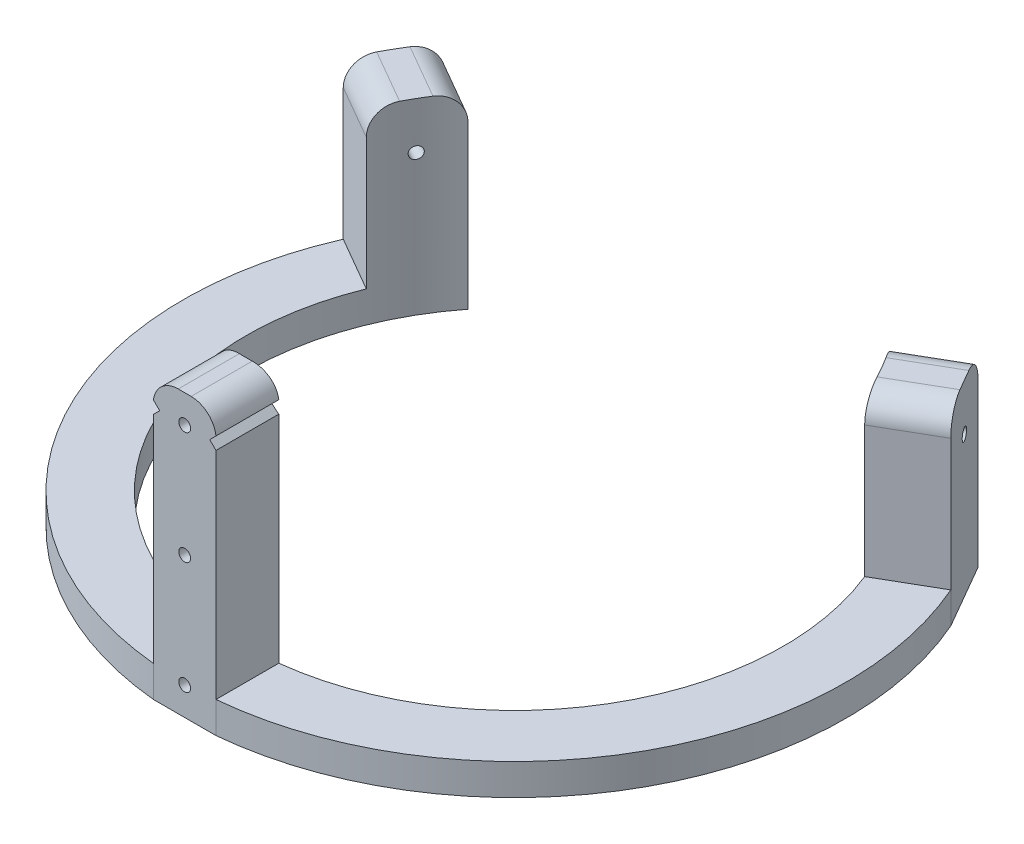
SolidWorks part; units mm, degrees
ref_plane "Front Plane" through (0, 0, 0) normal (0, 0, 1) x (1, 0, 0)
ref_plane "Top Plane" through (0, 0, 0) normal (0, 1, 0) x (1, 0, 0)
ref_plane "Right Plane" through (0, 0, 0) normal (1, 0, 0) x (0, 0, -1)
sketch "Sketch1" plane through (0, 0, 0) normal (0, 1, 0) x (1, 0, 0)
  circle A0 centre (0, 0) radius 54.61
  circle A2 centre (0, 0) radius 67.31
  dimension "D1" = 109.22
  dimension "D2" = 12.7
extrude "Boss-Extrude1" add sketch "Sketch1" along normal blind 57.15
ref_plane "Plane1" through (0, 0, 67.31) normal (0, 0, 1) x (1, 0, 0)
sketch "Sketch2" plane through (0, 0, 67.31) normal (0, 0, 1) x (1, 0, 0)
  line L0 (0, 57.15) -> (0, 0) construction
  line L1 (67.31, 57.15) -> (-67.31, 57.15) construction
  line L2 (0, 51.435) -> (5.08, 51.435) construction
  line L3 (0, 51.435) -> (-5.08, 51.435) construction
  line L4 (-6.35, 57.15) -> (-6.35, 52.705)
  line L5 (54.61, 57.15) -> (-54.61, 57.15) construction
  line L6 (-6.35, 52.705) -> (-5.08, 51.435)
  line L7 (-5.08, 51.435) -> (-6.35, 50.165)
  line L8 (-6.35, 50.165) -> (-6.35, 0)
  line L9 (-67.31, 0) -> (67.31, 0) construction
  line L10 (6.35, 0) -> (6.35, 50.165)
  line L11 (6.35, 50.165) -> (5.08, 51.435)
  line L12 (5.08, 51.435) -> (6.35, 52.705)
  line L13 (6.35, 52.705) -> (6.35, 57.15)
  line L15 (-6.35, 25.0825) -> (-19.05, 25.0825)
  line L16 (-6.35, 25.0825) -> (-6.35, 57.15)
  line L17 (-6.35, 57.15) -> (-19.05, 57.15)
  line L18 (-19.05, 25.0825) -> (-19.05, 57.15)
  line L19 (6.35, 25.0825) -> (19.05, 25.0825)
  line L20 (6.35, 25.0825) -> (6.35, 57.15)
  line L21 (6.35, 57.15) -> (19.05, 57.15)
  line L22 (19.05, 25.0825) -> (19.05, 57.15)
  circle A0 centre (0, 28.575) radius 1.2065
  circle A1 centre (0, 51.435) radius 1.2065
  circle A2 centre (0, 5.715) radius 1.2065
  dimension "D1" = 22.86
  dimension "D3" = 2.413
  dimension "D4" = 2.413
  dimension "D5" = 2.413
  dimension "D2" = 22.86
  dimension "D6" = 5.08
  dimension "D7" = 5.08
  dimension "D8" = 6.35
  dimension "D9" = 6.35
  dimension "D10" = 1.27
  dimension "D11" = 1.27
  dimension "D12" = 12.7
  dimension "D13" = 12.7
extrude "Cut-Extrude1" cut sketch "Sketch2" against normal through all both and the other way through all contours L16 L7 L6 | L18 L15 L8 L16 L4 L17 | L11 L20 L12 | L19 L22 L21 L13 L20 L10 | A1 | A0 | A2 region at (-12.7, 41.1162, 67.31) region at (-5.9267, 51.435, 67.31) region at (12.7, 41.1162, 67.31) region at (5.9267, 51.435, 67.31) region at (0, 28.575, 67.31) region at (0, 51.435, 67.31) region at (0, 5.715, 67.31)
ref_plane "Plane2" through (-58.2922, 0, -33.655) normal (-0.866, 0, -0.5) x (0, -1, 0)
sketch "Sketch3" plane through (-58.2922, 0, -33.655) normal (-0.866, 0, -0.5) x (0, -1, 0)
  line L0 (0, 0) -> (-57.15, 0) construction
  line L1 (0, -67.31) -> (0, 67.31) construction
  line L2 (-57.15, 67.31) -> (-57.15, -46.3839) construction
  line L3 (0, 0) -> (0, 67.31) construction
  line L4 (0, -67.31) -> (0, 67.31)
  circle A0 centre (-28.575, 0) radius 1.2065
  dimension "D1" = 2.413
extrude "Cut-Extrude2" cut sketch "Sketch3" against normal through all contours A0 region at (-58.2922, 28.575, -33.655)
mirror "Mirror1" about plane through (0, 0, 0) normal (1, 0, 0) of "Cut-Extrude2"
sketch "Sketch4" plane through (0, 57.15, 0) normal (0, 1, 0) x (1, 0, 0)
  line L0 (-54.1454, 39.9864) -> (-61.7019, 26.8981)
  line L1 (-54.1454, 39.9864) -> (8.8043, 3.6423)
  line L2 (-61.7019, 26.8981) -> (1.2478, -9.4459)
  line L3 (8.8043, 3.6423) -> (1.2478, -9.4459)
  line L4 (54.1454, 39.9864) -> (61.7019, 26.8981)
  line L5 (54.1454, 39.9864) -> (-5.4979, 5.5513)
  line L6 (61.7019, 26.8981) -> (2.0586, -7.537)
  line L7 (-5.4979, 5.5513) -> (2.0586, -7.537)
  line L8 (-6.35, -67.0098) -> (6.35, -67.0098)
  line L9 (-6.35, -67.0098) -> (-6.35, -1.2336)
  line L10 (6.35, -67.0098) -> (6.35, -1.2336)
  line L11 (-6.35, -1.2336) -> (6.35, -1.2336)
  arc A0 (58.8861, 32.6047) -> (57.6796, 34.6945) centre (0, 0) ccw construction
  arc A1 (-57.6796, 34.6945) -> (-58.8861, 32.6047) centre (0, 0) ccw construction
  arc A2 (58.8861, 32.6047) -> (57.6796, 34.6945) centre (0, 0) ccw
  arc A3 (-57.6796, 34.6945) -> (-58.8861, 32.6047) centre (0, 0) ccw
  arc A4 (19.05, -64.558) -> (19.05, 64.558) centre (0, 0) ccw construction
  arc A5 (-19.05, 64.558) -> (-19.05, -64.558) centre (0, 0) ccw construction
  circle A6 centre (0, 0) radius 109.8549
  arc M7 (-19.05, 64.558) -> (-19.05, -64.558) centre (0, 0) ccw
  line M8 (-19.05, -64.558) -> (-19.05, -51.1796)
  arc M9 (-19.05, -51.1796) -> (-19.05, 51.1796) centre (0, 0) cw
  line M10 (-19.05, 51.1796) -> (-19.05, 64.558)
  dimension "D1" = 6.35
  dimension "D2" = 6.35
  dimension "D3" = 6.35
  dimension "D4" = 6.35
extrude "Cut-Extrude3" cut sketch "Sketch4" against normal blind 50.8 contours A6 L10 L8 L9 L2 L1 L5 L4 L6 | L2 M7 M8 M9 | L1 M7 M9 M10 region at (-35.0848, 57.15, -49.1687) region at (-56.6765, 57.15, -22.8026) region at (-106.7478, 57.15, 0)
sketch "Sketch5" plane through (0, 6.35, 0) normal (0, 1, 0) x (1, 0, 0)
  line L0 (6.35, -54.2396) -> (-6.35, -54.2396)
  line L1 (6.35, -54.2396) -> (6.35, 98.2339)
  line L2 (-6.35, -54.2396) -> (-6.35, 98.2339)
  line L3 (6.35, 98.2339) -> (-6.35, 98.2339)
  line L4 (6.35, -54.2396) -> (6.35, -67.0098) construction
  arc A0 (-6.35, -54.2396) -> (6.35, -54.2396) centre (0, 0) ccw construction
  point P7 (6.35, -7.9745)
  point P8 (6.35, 98.2339)
extrude "Cut-Extrude4" cut sketch "Sketch5" against normal blind 50.8
sketch "Sketch6" plane through (0, 57.15, 0) normal (0, 1, 0) x (1, 0, 0)
  line L0 (50.6169, 20.4982) -> (61.7019, 26.8981) construction
  line L1 (61.7019, 26.8981) -> (54.1454, 39.9864) construction
  line L2 (54.1454, 39.9864) -> (43.0604, 33.5865) construction
  line L3 (-61.7019, 26.8981) -> (-50.6169, 20.4982) construction
  line L4 (-43.0604, 33.5865) -> (-54.1454, 39.9864) construction
  line L5 (50.6169, 20.4982) -> (61.7019, 26.8981)
  line L6 (61.7019, 26.8981) -> (54.1454, 39.9864)
  line L7 (54.1454, 39.9864) -> (43.0604, 33.5865)
  line L8 (-61.7019, 26.8981) -> (-50.6169, 20.4982)
  line L9 (-43.0604, 33.5865) -> (-54.1454, 39.9864)
  arc A0 (50.6169, 20.4982) -> (43.0604, 33.5865) centre (0, 0) ccw construction
  arc A1 (-54.1454, 39.9864) -> (-61.7019, 26.8981) centre (0, 0) ccw construction
  arc A2 (-43.0604, 33.5865) -> (-50.6169, 20.4982) centre (0, 0) ccw construction
  arc A3 (50.6169, 20.4982) -> (43.0604, 33.5865) centre (0, 0) ccw
  arc A4 (-54.1454, 39.9864) -> (-61.7019, 26.8981) centre (0, 0) ccw
  arc A5 (-43.0604, 33.5865) -> (-50.6169, 20.4982) centre (0, 0) ccw
extrude "Cut-Extrude5" cut sketch "Sketch6" against normal blind 19.05
sketch "Sketch7" plane through (0, 6.35, 0) normal (0, 1, 0) x (1, 0, 0)
  line L0 (6.35, 67.0098) -> (6.35, 54.2396) construction
  line L1 (43.0604, 33.5865) -> (54.1454, 39.9864) construction
  line L2 (-6.35, 54.2396) -> (-6.35, 67.0098) construction
  line L3 (-54.1454, 39.9864) -> (-43.0604, 33.5865) construction
  line L4 (6.35, 67.0098) -> (6.35, 54.2396)
  line L5 (43.0604, 33.5865) -> (54.1454, 39.9864)
  line L6 (-6.35, 54.2396) -> (-6.35, 67.0098)
  line L7 (-54.1454, 39.9864) -> (-43.0604, 33.5865)
  arc A0 (43.0604, 33.5865) -> (6.35, 54.2396) centre (0, 0) ccw construction
  arc A1 (54.1454, 39.9864) -> (6.35, 67.0098) centre (0, 0) ccw construction
  arc A2 (-6.35, 67.0098) -> (-54.1454, 39.9864) centre (0, 0) ccw construction
  arc A3 (-6.35, 54.2396) -> (-43.0604, 33.5865) centre (0, 0) ccw construction
  arc A4 (43.0604, 33.5865) -> (6.35, 54.2396) centre (0, 0) ccw
  arc A5 (54.1454, 39.9864) -> (6.35, 67.0098) centre (0, 0) ccw
  arc A6 (-6.35, 67.0098) -> (-54.1454, 39.9864) centre (0, 0) ccw
  arc A7 (-6.35, 54.2396) -> (-43.0604, 33.5865) centre (0, 0) ccw
extrude "Cut-Extrude6" cut sketch "Sketch7" against normal blind 19.05
fillet "Fillet1" radius 5.08 6 edges at (-6.35, 57.15, 60.6247) (6.35, 57.15, 60.6247) (56.1594, 38.1, -23.6982) (48.6029, 38.1, -36.7864) (-56.1594, 38.1, -23.6982) (-48.6029, 38.1, -36.7864)
sketch "Sketch8" plane through (0, 6.35, 0) normal (0, 1, 0) x (1, 0, 0)
  line L5 (-1.0259, -67.3022) -> (-1.0259, -67.0098) construction
  line L6 (-1.0259, -67.0098) -> (-6.35, -67.0098) construction
  line L7 (1.0259, -67.0098) -> (1.0259, -67.3022) construction
  line L8 (6.35, -67.0098) -> (1.0259, -67.0098) construction
  line L9 (54.1454, 39.9864) -> (61.7019, 26.8981) construction
  line L10 (-1.0259, -67.3022) -> (-1.0259, -67.0098)
  line L11 (-1.0259, -67.0098) -> (-6.35, -67.0098)
  line L12 (1.0259, -67.0098) -> (1.0259, -67.3022)
  line L13 (6.35, -67.0098) -> (1.0259, -67.0098)
  line L14 (54.1454, 39.9864) -> (61.7019, 26.8981)
  line L15 (-1.0259, -67.0098) -> (1.0259, -67.0098)
  line L16 (1.0259, -67.3022) -> (0.9722, -68.1805)
  line L17 (0.9722, -68.1805) -> (-1.552, -68.2322)
  line L18 (-1.552, -68.2322) -> (-1.0259, -67.3022)
  arc A3 (-6.35, -67.0098) -> (-1.0259, -67.3022) centre (0, 0) ccw construction
  arc A4 (1.0259, -67.3022) -> (6.35, -67.0098) centre (0, 0) ccw construction
  arc A5 (61.7019, 26.8981) -> (54.1454, 39.9864) centre (0, 0) ccw construction
  arc A6 (-6.35, -67.0098) -> (-1.0259, -67.3022) centre (0, 0) ccw
  arc A7 (1.0259, -67.3022) -> (6.35, -67.0098) centre (0, 0) ccw
  arc A8 (61.7019, 26.8981) -> (54.1454, 39.9864) centre (0, 0) ccw
  arc M1 (61.7019, 26.8981) -> (54.1454, 39.9864) centre (0, 0) ccw
  line M2 (54.1454, 39.9864) -> (61.7019, 26.8981)
extrude "Cut-Extrude7" cut sketch "Sketch8" against normal blind 19.05 contours M2 M1 | L11 A6 L10 | L18 L17 L16 L12 L15 L10 | L12 A7 L13 region at (-2.9733, 6.35, 67.1208) region at (-0.1236, 6.35, 67.6311) region at (2.9733, 6.35, 67.1208) region at (58.0711, 6.35, -33.5274)
